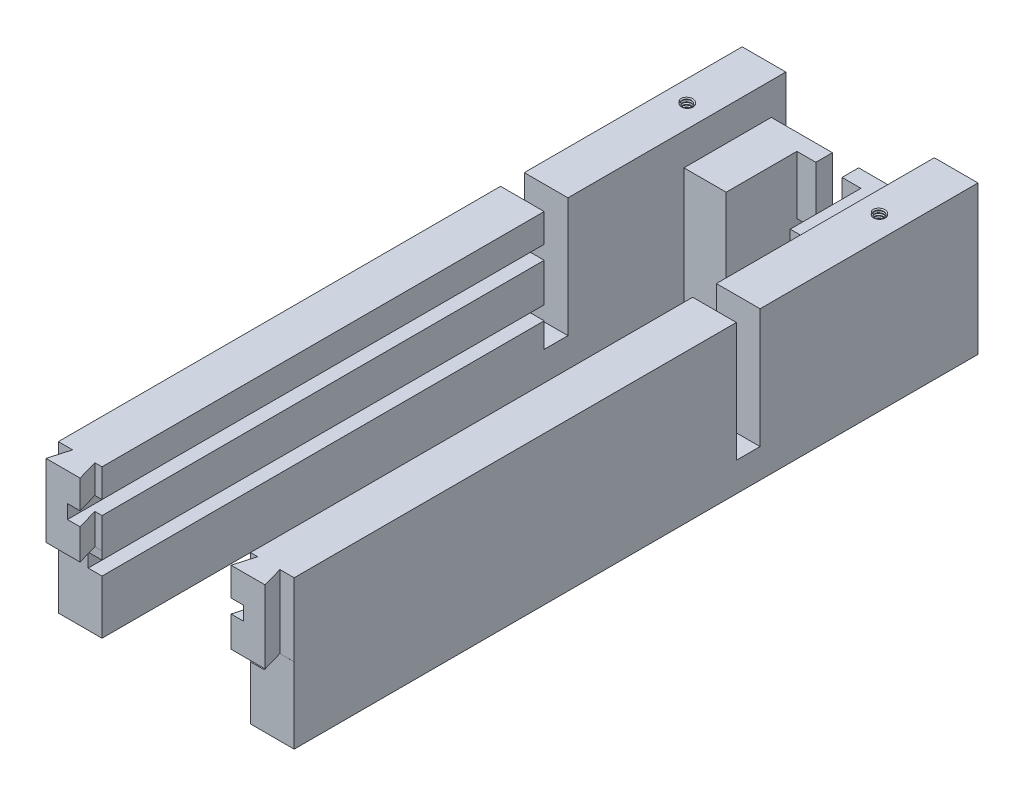
SolidWorks part; units mm, degrees
ref_plane "Front Plane" through (0, 0, 0) normal (0, 0, 1) x (1, 0, 0)
ref_plane "Top Plane" through (0, 0, 0) normal (0, 1, 0) x (1, 0, 0)
ref_plane "Right Plane" through (0, 0, 0) normal (1, 0, 0) x (0, 0, -1)
sketch "Sketch1" plane through (0, 0, 0) normal (1, 0, 0) x (0, 0, -1)
  line L1 (-64.5621, 30.5573) -> (177.4379, 30.5573)
  line L2 (-64.5621, 30.5573) -> (-64.5621, -20.4427)
  line L3 (-64.5621, -20.4427) -> (177.4379, -20.4427)
  line L4 (177.4379, 30.5573) -> (177.4379, -20.4427)
  dimension "D1" = 242
  dimension "D2" = 51
extrude "Boss-Extrude1" add sketch "Sketch1" along normal blind 15 contours L2 L3 L4 L1
sketch "Sketch26" plane through (0, 0, 0) normal (-1, 0, 0) x (0, 0, 1)
  line L1 (-172.4379, 19.5573) -> (-142.4379, 19.5573)
  line L2 (-172.4379, 19.5573) -> (-172.4379, -20.4427)
  line L3 (-172.4379, -20.4427) -> (-142.4379, -20.4427)
  line L4 (-142.4379, 19.5573) -> (-142.4379, -20.4427)
  line L5 (64.5621, -20.4427) -> (-177.4379, -20.4427) construction
  line L6 (-177.4379, 30.5573) -> (-177.4379, -20.4427) construction
  dimension "D1" = 5
  dimension "D2" = 30
  dimension "D3" = 40
extrude "Boss-Extrude3" add sketch "Sketch26" against normal blind 29.5
sketch "Sketch28" plane through (29.5, 0, 0) normal (1, 0, 0) x (0, 0, -1)
  line L0 (147.0417, -20.4427) -> (147.0417, -10.6927)
  line L1 (172.4379, -20.4427) -> (142.4379, -20.4427) construction
  line L2 (147.0417, -10.6927) -> (162.0417, -10.6927)
  line L3 (162.0417, -10.6927) -> (162.0417, -20.4427)
  line L4 (162.0417, -20.4427) -> (147.0417, -20.4427)
  dimension "D1" = 9.75
  dimension "D2" = 15
extrude "Boss-Extrude5" add sketch "Sketch28" along normal blind 4.5
sketch "Sketch29" plane through (29.5, 0, 0) normal (1, 0, 0) x (0, 0, -1)
  line L0 (172.4379, 19.5573) -> (166.7379, 19.5573)
  line L1 (142.4379, 19.5573) -> (172.4379, 19.5573) construction
  line L2 (166.7379, 19.5573) -> (166.7379, -0.4427)
  line L3 (166.7379, -0.4427) -> (172.4379, -0.4427)
  line L4 (172.4379, 19.5573) -> (172.4379, -20.4427) construction
  line L5 (172.4379, -0.4427) -> (172.4379, 19.5573)
  dimension "D1" = 20
  dimension "D2" = 5.7
extrude "Boss-Extrude6" add sketch "Sketch29" along normal blind 6.5
sketch "Sketch12" plane through (0, 30.5573, 0) normal (0, 1, 0) x (1, 0, 0)
  line L0 (0, -57.4487) -> (4.9097, -57.4487)
  line L1 (0, -64.5621) -> (0, 177.4379) construction
  line L2 (4.9097, -57.4487) -> (2.87, -64.5621)
  line L3 (15, -64.5621) -> (0, -64.5621) construction
  line L4 (2.87, -64.5621) -> (0, -64.5621)
  line L5 (0, -64.5621) -> (0, -57.4487)
  line L6 (15, -57.4487) -> (15, -64.5621)
  line L7 (15, -64.5621) -> (15, 177.4379) construction
  line L8 (15, -64.5621) -> (14.57, -64.5621)
  line L9 (14.57, -64.5621) -> (12.5303, -57.4487)
  line L10 (12.5303, -57.4487) -> (15, -57.4487)
  dimension "D1" = 7.4
  dimension "D2" = 7.4
  dimension "D3" = 106
  dimension "D4" = 106
  dimension "D5" = 11.7
  dimension "D6" = 2.87
extrude "Cut-Extrude8" cut sketch "Sketch12" against normal blind 25
sketch "Sketch13" plane through (0, -20.4427, 0) normal (0, -1, 0) x (1, 0, 0)
  line L0 (15, 64.5621) -> (15, -142.4379) construction
  line L1 (0, 64.5621) -> (15, 64.5621)
  line L2 (0, 64.5621) -> (0, 57.4521)
  line L3 (0, 57.4521) -> (15, 57.4521)
  line L4 (15, 64.5621) -> (15, 57.4521)
  dimension "D1" = 7.11
extrude "Cut-Extrude9" cut sketch "Sketch13" against normal blind 26
sketch "Sketch17" plane through (0, 30.5573, 0) normal (0, 1, 0) x (1, 0, 0)
  line L0 (15, -57.4487) -> (15, 177.4379) construction
  line L1 (0, 110.4379) -> (15, 110.4379)
  line L2 (0, 110.4379) -> (0, 102.5879)
  line L3 (0, 102.5879) -> (15, 102.5879)
  line L4 (15, 110.4379) -> (15, 102.5879)
  line L6 (0, 102.5879) -> (15, 102.5879)
  line L7 (0, 102.5879) -> (0, 94.4379)
  line L8 (0, 94.4379) -> (15, 94.4379)
  line L9 (15, 102.5879) -> (15, 94.4379)
  line M14 (15, -57.4487) -> (15, 177.4379)
  line M16 (0, 177.4379) -> (0, -57.4487)
  dimension "D1" = 7.85
  dimension "D2" = 8.15
extrude "Cut-Extrude10" cut sketch "Sketch17" against normal blind 41 contours L8 L3 M16 M14 region at (7.5, 30.5573, -98.5129)
sketch "Sketch7" plane through (0, 0, -94.4379) normal (0, 0, -1) x (-1, 0, 0)
  line L0 (-15, -20.4427) -> (-15, -1.9427)
  line L1 (-15, 2.8073) -> (-15, 16.0573)
  line L2 (-10.25, 2.8073) -> (-15, 2.8073)
  line L3 (-10.25, 2.8073) -> (-10.25, -1.9427)
  line L4 (-10.25, -1.9427) -> (-15, -1.9427)
  line L5 (-15, 2.8073) -> (-15, -1.9427)
  line L6 (-15, 30.5573) -> (-15, -20.4427) construction
  line L8 (-15, 16.0573) -> (-10.25, 16.0573)
  line L9 (-15, 16.0573) -> (-15, 20.8073)
  line L10 (-15, 20.8073) -> (-10.25, 20.8073)
  line L11 (-10.25, 16.0573) -> (-10.25, 20.8073)
  dimension "D1" = 18.5
  dimension "D2" = 4.75
  dimension "D3" = 4.75
  dimension "D4" = 13.25
  dimension "D5" = 4.75
  dimension "D6" = 4.75
extrude "Cut-Extrude5" cut sketch "Sketch7" against normal blind 165 contours L4 L3 L2 | L9 L8 L11 L10 region at (12.625, 0.4323, -94.4379)
sketch "Sketch22" plane through (0, 30.5573, 0) normal (0, 1, 0) x (1, 0, 0)
  line L0 (15, 177.4379) -> (15, 161.9379)
  line L1 (15, 102.5879) -> (15, 177.4379) construction
  line L3 (15, 161.9379) -> (8, 161.9379)
  line L4 (15, 161.9379) -> (15, 158.7879)
  line L5 (15, 158.7879) -> (8, 158.7879)
  line L6 (8, 161.9379) -> (8, 158.7879)
  line M5 (15, 102.5879) -> (15, 177.4379)
  dimension "D1" = 15.5
  dimension "D2" = 7
  dimension "D3" = 3.15
extrude "Cut-Extrude13" [suppressed] cut sketch "Sketch22" against normal blind 45 contours L3 L6 L5 M5
ref_plane "Plane1" through (40.5, 0, 0) normal (1, 0, 0) x (0, 0, -1)
sketch "Sketch18" [suppressed] plane through (0, 30.5573, 0) normal (0, 1, 0) x (1, 0, 0)
  line L0 (15, 102.5879) -> (15, 136.5879)
  line L1 (15, 102.5879) -> (15, 177.4379) construction
  line L3 (15, 136.5879) -> (10, 136.5879)
  line L4 (15, 136.5879) -> (15, 144.0879)
  line L5 (15, 144.0879) -> (10, 144.0879)
  line L6 (10, 136.5879) -> (10, 144.0879)
  line M6 (15, 102.5879) -> (15, 177.4379)
  dimension "D1" = 34
  dimension "D2" = 5
  dimension "D3" = 7.5
extrude "Cut-Extrude11" [suppressed] cut sketch "Sketch18" against normal blind 38 contours L6 L3 L5 M6
sketch "Sketch23" [suppressed] plane through (0, 0, -177.4379) normal (0, 0, -1) x (-1, 0, 0)
  line L0 (-15, -20.4427) -> (-15, 9.0573)
  line L1 (-15, 30.5573) -> (-15, -20.4427) construction
  line L3 (-15, 9.0573) -> (-10.5, 9.0573)
  line L4 (-15, 9.0573) -> (-15, 13.5573)
  line L5 (-15, 13.5573) -> (-10.5, 13.5573)
  line L6 (-10.5, 9.0573) -> (-10.5, 13.5573)
  line M5 (-15, 30.5573) -> (-15, -20.4427)
  dimension "D1" = 4.5
  dimension "D2" = 4.5
  dimension "D3" = 29.5
extrude "Cut-Extrude14" [suppressed] cut sketch "Sketch23" against normal blind 45 contours L3 L6 L5 M5
mirror "Mirror4" about plane through (40.5, 0, 0) normal (1, 0, 0) of bodies 107 113
sketch "Sketch30" plane through (0, 30.5573, 0) normal (0, 1, 0) x (1, 0, 0)
  circle A0 centre (73.5, 151.0787) radius 2
  circle A1 centre (7.5, 151.0787) radius 2
extrude "Cut-Extrude15" cut sketch "Sketch30" against normal blind 10
thread "Thread1" pitch 0.7937 method extrude profile "Thread Profile1" start angle 0, offset 0, length 10, pitch 0.7937, diameter 4
ref_plane "Plane2" through (9.5, 20.5573, -151.0787) normal (0, 0, 1) x (1, 0, 0)
sketch "Thread Profile1" plane through (9.5, 20.5573, -151.0787) normal (0, 0, 1) x (1, 0, 0)
  line L0 (0, 0) -> (0, 0.7937) construction
  line L11 (0, 0) -> (0, 0.6945)
  line L12 (0, 0.6945) -> (-0.4296, 0.4465)
  line L13 (-0.4296, 0.4465) -> (-0.4296, 0.248)
  line L15 (-0.4296, 0.248) -> (0, 0)
  line L17 (-0.4296, 0.3473) -> (0, 0.3473) construction
  point P2 (0, 0)
  dimension "Pitch" = 0.7937
  dimension "Profile_Angle" = 60
  dimension "Profile_Land" = 0.1984
  dimension "Profile_Height" = 0.4296
thread "Thread2" pitch 0.7937 method extrude profile "Thread Profile2" start angle 0, offset 0, length 10, pitch 0.7937, diameter 4
ref_plane "Plane3" through (75.5, 20.5573, -151.0787) normal (0, 0, 1) x (1, 0, 0)
sketch "Thread Profile2" plane through (75.5, 20.5573, -151.0787) normal (0, 0, 1) x (1, 0, 0)
  line L0 (0, 0) -> (0, 0.7937) construction
  line L11 (0, 0) -> (0, 0.6945)
  line L12 (0, 0.6945) -> (-0.4296, 0.4465)
  line L13 (-0.4296, 0.4465) -> (-0.4296, 0.248)
  line L15 (-0.4296, 0.248) -> (0, 0)
  line L17 (-0.4296, 0.3473) -> (0, 0.3473) construction
  point P2 (0, 0)
  dimension "Pitch" = 0.7937
  dimension "Profile_Angle" = 60
  dimension "Profile_Land" = 0.1984
  dimension "Profile_Height" = 0.4296
